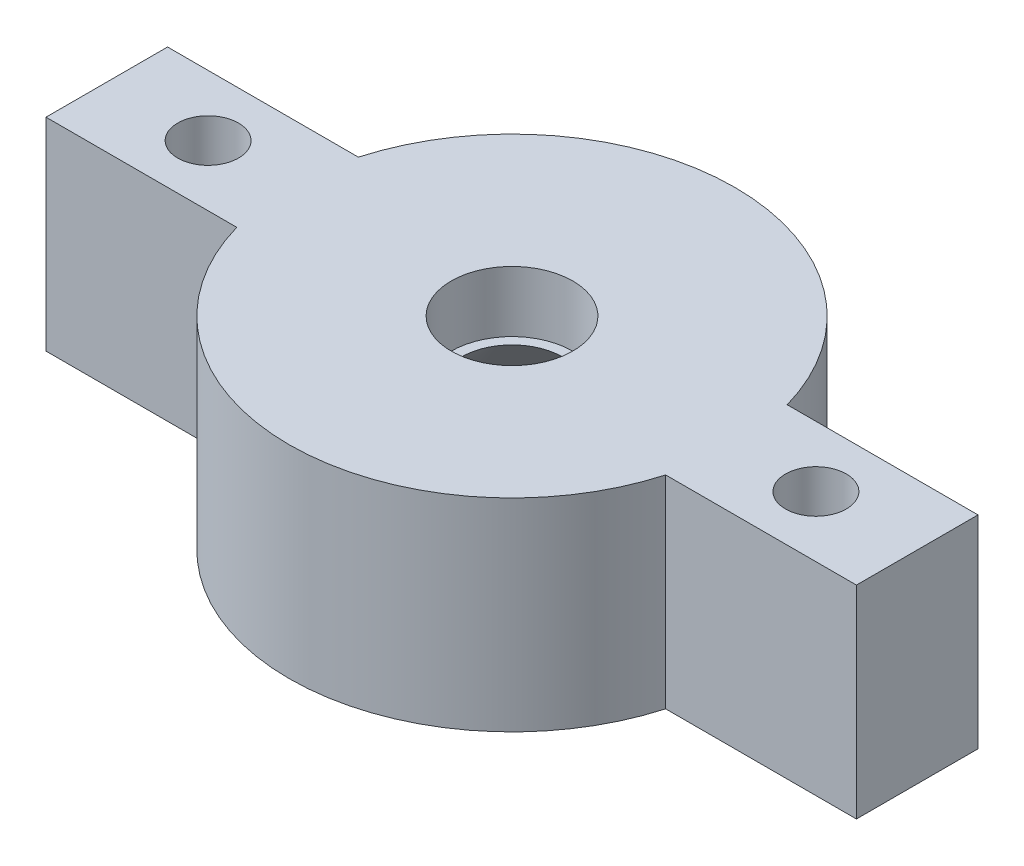
SolidWorks part; units mm, degrees
ref_plane "Front Plane" through (0, 0, 0) normal (0, 0, 1) x (1, 0, 0)
ref_plane "Top Plane" through (0, 0, 0) normal (0, 1, 0) x (1, 0, 0)
ref_plane "Right Plane" through (0, 0, 0) normal (1, 0, 0) x (0, 0, -1)
sketch "Sketch2" plane through (0, 0, 0) normal (1, 0, 0) x (0, 0, -1)
  line L1 (-3, -5) -> (3, -5)
  line L2 (-3, -5) -> (-3, 5)
  line L3 (-3, 5) -> (3, 5)
  line L4 (3, -5) -> (3, 5)
  line L5 (-3, -5) -> (3, 5) construction
  line L6 (-3, 5) -> (3, -5) construction
  point P0 (0, 0)
  dimension "D1" = 6
  dimension "D2" = 10
extrude "Boss-Extrude1" add sketch "Sketch2" along normal blind 40
sketch "Sketch3" plane through (0, 5, 0) normal (0, 1, 0) x (1, 0, 0)
  line L0 (0, 0) -> (40, 0) construction
  line L1 (40, 3) -> (40, -3) construction
  circle A0 centre (20, 0) radius 11
  dimension "D1" = 22
extrude "Boss-Extrude2" add sketch "Sketch3" against normal up to surface (10 mm away) up to face at (20, -5, 0)
sketch "Sketch4" plane through (0, -5, 0) normal (0, -1, 0) x (-1, 0, 0)
  circle A0 centre (-20, 0) radius 7.5
  circle A1 centre (-20, 0) radius 11 construction
  dimension "D1" = 15
extrude "Cut-Extrude1" cut sketch "Sketch4" against normal blind 2
sketch "Sketch5" plane through (0, 0, 0) normal (0, 0, -1) x (-1, 0, 0)
  line L0 (-20, -3) -> (-27.5, -3)
  line L2 (-27.5, -3) -> (-22.5, 2)
  line L3 (-22.5, 2) -> (-20, 2)
  line L5 (-20, 2) -> (-20, -3)
  line L6 (-30.583, -5) -> (-9.417, -5) construction
  line L7 (-9.417, 5) -> (-30.583, 5) construction
  point P10 (-20, 5)
  dimension "D1" = 2
  dimension "D2" = 7.5
  dimension "D3" = 2.5
  dimension "D4" = 5
revolve "Cut-Revolve1" cut sketch "Sketch5" angle 360 about L5
sketch "Sketch6" plane through (0, 2, 0) normal (0, -1, 0) x (1, 0, 0)
  circle A0 centre (20, 0) radius 3
  circle A1 centre (20, 0) radius 2.5
  circle A2 centre (20, 0) radius 2.5 construction
  dimension "D2" = 0.5
  dimension "D1" = 0
extrude "Cut-Extrude2" cut sketch "Sketch6" against normal blind 13
fillet "Fillet1" radius 2 1 edges at (20, -5, -7.5)
sketch "Sketch7" plane through (0, -5, 0) normal (0, -1, 0) x (1, 0, 0)
  line L0 (0, 3) -> (0, -3) construction
  line L1 (20, 11) -> (20, -11) construction
  circle A0 centre (5, 0) radius 1.5
  arc A1 (30.583, 3) -> (9.417, 3) centre (20, 0) ccw construction
  arc A2 (9.417, -3) -> (30.583, -3) centre (20, 0) ccw construction
  circle A3 centre (35, 0) radius 1.5
  dimension "D1" = 3
  dimension "D2" = 5
extrude "Cut-Extrude3" cut sketch "Sketch7" against normal up to next
